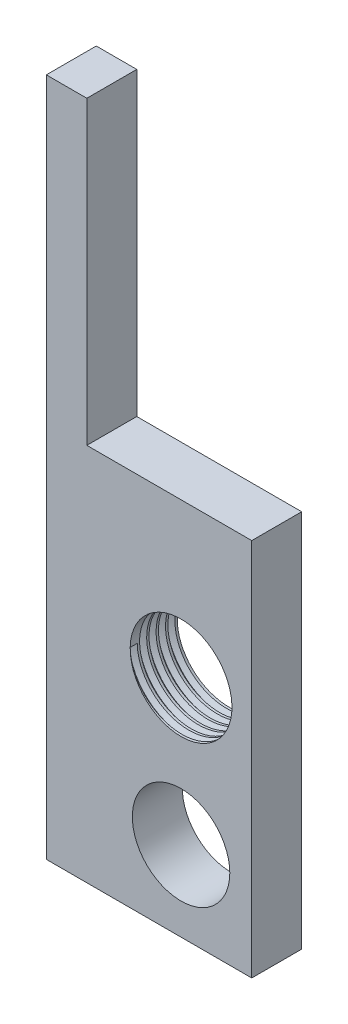
SolidWorks part; units mm, degrees
ref_plane "Front Plane" through (0, 0, 0) normal (0, 0, 1) x (1, 0, 0)
ref_plane "Top Plane" through (0, 0, 0) normal (0, 1, 0) x (1, 0, 0)
ref_plane "Right Plane" through (0, 0, 0) normal (1, 0, 0) x (0, 0, -1)
sketch "Sketch1" plane through (0, 0, 0) normal (0, 0, 1) x (1, 0, 0)
  line L0 (0, 0) -> (0, 72.1)
  line L1 (0, 72.1) -> (4.3, 72.1)
  line L2 (4.3, 72.1) -> (4.3, 40.2)
  line L3 (4.3, 40.2) -> (21.8, 40.2)
  line L4 (21.8, 40.2) -> (21.8, 0)
  line L5 (21.8, 0) -> (0, 0)
  line L6 (0, 18.855) -> (14.3, 18.855) construction
  line L7 (14.3, 40.2) -> (14.3, 0) construction
  line L8 (14.3, 0) -> (14.3, 8.4908) construction
  line L9 (14.3, 13.6618) -> (14.3, 30.4888) construction
  line L10 (14.3, 13.6618) -> (14.3, 23.8377) construction
  line L11 (14.219, 0.0858) -> (14.1273, 8.4308) construction
  line L12 (14.262, 13.6082) -> (14.1112, 23.8624) construction
  circle A0 centre (14.3, 8.4908) radius 5.171
  circle A1 centre (14.3, 23.8377) radius 5.4
  dimension "D6" = 10.8
  dimension "D1" = 4.3
  dimension "D2" = 40.2
  dimension "D3" = 72.1
  dimension "D4" = 21.8
  dimension "D5" = 14.3
extrude "Boss-Extrude1" add sketch "Sketch1" along normal blind 5.3
thread "Thread1" start angle 1, offset 0, length 0, pitch 1, diameter 10.8
ref_plane "Plane1" through (8.9008, 23.9319, 5.3) normal (-0.0175, -0.9998, 0) x (-0.9998, 0.0175, 0)
sketch "Thread Profile1" plane through (8.9008, 23.9319, 5.3) normal (-0.0175, -0.9998, 0) x (-0.9998, 0.0175, 0)
  line L0 (0, 0) -> (0, 1) construction
  line L1 (0, 0) -> (0.5413, 0.3125)
  line L2 (0.5413, 0.3125) -> (0.5413, 0.4375)
  line L3 (0.5413, 0.4375) -> (0, 0.75)
  line L4 (0.5413, 0.375) -> (0, 0.375) construction
  line L11 (0, 0) -> (0, 0.75)
  point P2 (0, 0)
  dimension "Pitch" = 1
  dimension "Profile_Angle" = 60
  dimension "Profile_Land" = 0.125
  dimension "Profile_Height" = 0.5413
